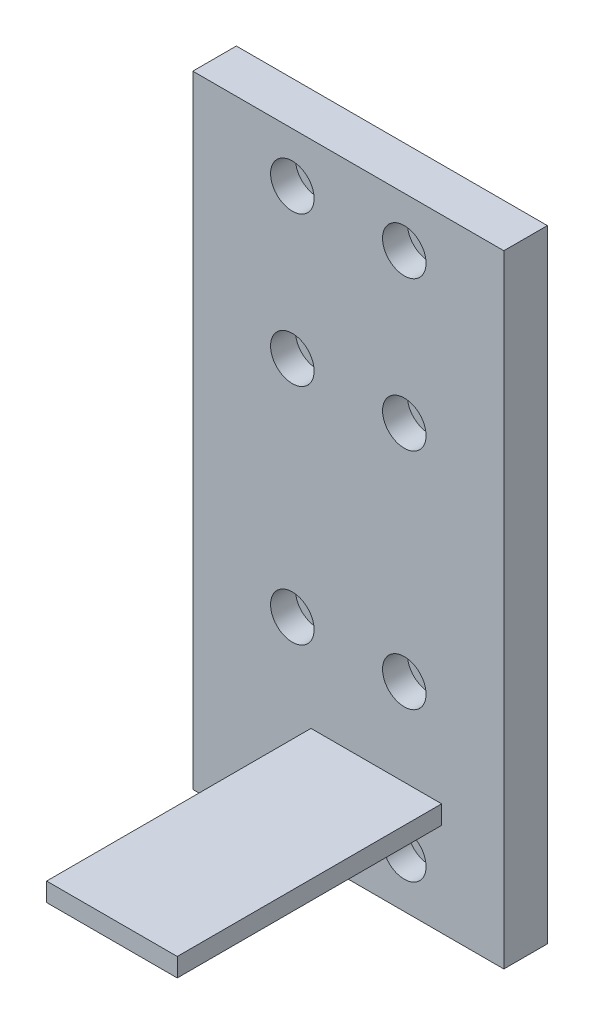
SolidWorks part; units mm, degrees
ref_plane "Front Plane" through (0, 0, 0) normal (0, 0, 1) x (1, 0, 0)
ref_plane "Top Plane" through (0, 0, 0) normal (0, 1, 0) x (1, 0, 0)
ref_plane "Right Plane" through (0, 0, 0) normal (1, 0, 0) x (0, 0, -1)
sketch "Sketch1" plane through (0, 0, 0) normal (0, 0, 1) x (1, 0, 0)
  line L1 (-25, -50) -> (25, -50)
  line L2 (-25, -50) -> (-25, 50)
  line L3 (-25, 50) -> (25, 50)
  line L4 (25, -50) -> (25, 50)
  line L5 (-25, -50) -> (25, 50) construction
  line L6 (-25, 50) -> (25, -50) construction
  point P0 (0, 0)
  dimension "D1" = 50
  dimension "D2" = 100
sketch "Sketch2" plane through (0, 0, 0) normal (0, 0, 1) x (1, 0, 0)
  line L0 (-9, 42) -> (9, 42) construction
  line L1 (9, 42) -> (9, 18) construction
  line L2 (9, 18) -> (-9, 18) construction
  line L3 (-9, 18) -> (-9, 42) construction
  line L4 (-9, 42) -> (9, 18) construction
  line L5 (9, 42) -> (-9, 18) construction
  line L6 (-9, -18) -> (9, -18) construction
  line L7 (9, -18) -> (9, -42) construction
  line L8 (9, -42) -> (-9, -42) construction
  line L9 (-9, -42) -> (-9, -18) construction
  line L10 (-9, -18) -> (9, -42) construction
  line L11 (9, -18) -> (-9, -42) construction
  line L12 (-9, 18) -> (-9, -18) construction
  line L13 (-9, -18) -> (9, 18) construction
  line L14 (9, 18) -> (9, -18) construction
  line L15 (9, -18) -> (-9, 18) construction
  circle A0 centre (-9, 42) radius 1.6
  circle A1 centre (9, 42) radius 1.6
  circle A2 centre (-9, 18) radius 1.6
  circle A3 centre (9, 18) radius 1.6
  circle A4 centre (9, -18) radius 1.6
  circle A5 centre (-9, -18) radius 1.6
  circle A6 centre (-9, -42) radius 1.6
  circle A7 centre (9, -42) radius 1.6
  point P2 (0, 0)
  point P5 (0, 0)
  dimension "D1" = 3.2
  dimension "D2" = 24
  dimension "D3" = 36
  dimension "D4" = 24
  dimension "D5" = 18
extrude "Boss-Extrude1" add sketch "Sketch1" against normal blind 7
extrude "Cut-Extrude1" cut sketch "Sketch2" against normal up to next
sketch "Sketch3" plane through (0, 0, 0) normal (0, 0, 1) x (1, 0, 0)
  line L0 (-9, 42) -> (9, 18) construction
  line L1 (9, 18) -> (9, 42) construction
  line L2 (9, 42) -> (-9, 18) construction
  line L3 (-9, 18) -> (-9, 42) construction
  line L4 (-9, 42) -> (9, 42) construction
  line L5 (-9, 18) -> (9, 18) construction
  line L6 (9, 18) -> (-9, -18) construction
  line L7 (-9, -18) -> (9, -18) construction
  line L8 (9, -18) -> (-9, 18) construction
  line L9 (-9, 18) -> (-9, -18) construction
  line L10 (-9, -18) -> (-9, -42) construction
  line L11 (-9, -42) -> (9, -42) construction
  line L12 (9, -42) -> (-9, -18) construction
  line L13 (9, 18) -> (9, -18) construction
  line L14 (9, -18) -> (9, -42) construction
  line L15 (9, -18) -> (-9, -42) construction
  circle A0 centre (-9, 42) radius 3.5
  circle A1 centre (9, 42) radius 3.5
  circle A2 centre (-9, 18) radius 3.5
  circle A3 centre (9, 18) radius 3.5
  circle A4 centre (-9, -18) radius 3.5
  circle A5 centre (9, -18) radius 3.5
  circle A6 centre (9, -42) radius 3.5
  circle A7 centre (-9, -42) radius 3.5
  point P24 (0, 0)
  point P25 (0, 0)
  dimension "D1" = 7
  dimension "D2" = 18
  dimension "D3" = 24
  dimension "D4" = 36
  dimension "D5" = 24
extrude "Cut-Extrude2" cut sketch "Sketch3" against normal blind 4
sketch "Sketch4" plane through (0, 0, 0) normal (0, 0, 1) x (1, 0, 0)
  line L0 (-25, -32) -> (25, -32) construction
  line L1 (-25, 50) -> (-25, -50) construction
  line L2 (25, -50) -> (25, 50) construction
  line L3 (-25, -35) -> (25, -35) construction
  line L4 (15, -32) -> (15, -35)
  line L5 (-6, -32) -> (-6, -35)
  line L6 (-6, -32) -> (15, -32)
  line L7 (15, -35) -> (-6, -35)
  dimension "D1" = 18
  dimension "D2" = 3
  dimension "D3" = 10
  dimension "D4" = 21
extrude "Boss-Extrude2" add sketch "Sketch4" along normal blind 42.5
